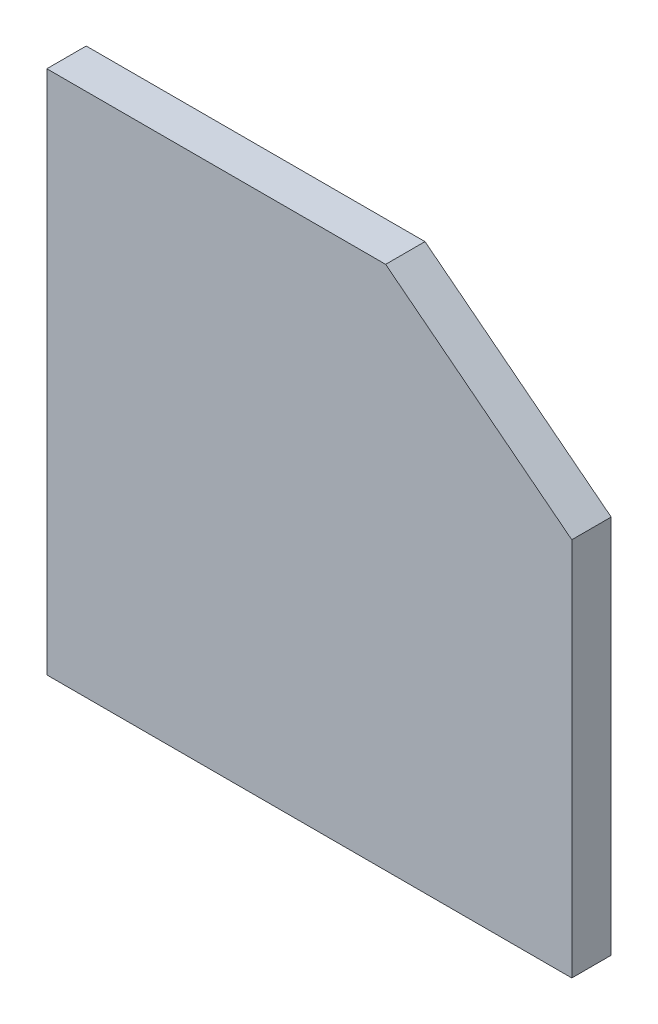
SolidWorks part; units mm, degrees
ref_plane "Front Plane" through (0, 0, 0) normal (0, 0, 1) x (1, 0, 0)
ref_plane "Top Plane" through (0, 0, 0) normal (0, 1, 0) x (1, 0, 0)
ref_plane "Right Plane" through (0, 0, 0) normal (1, 0, 0) x (0, 0, -1)
sketch "Sketch1" plane through (0, 0, 0) normal (0, 0, 1) x (1, 0, 0)
  line L0 (25.8158, 40) -> (40, 28.9181)
  line L1 (0, 0) -> (40, 0)
  line L2 (0, 0) -> (0, 40)
  line L3 (0, 40) -> (40, 40)
  line L4 (40, 0) -> (40, 40)
  dimension "D1" = 40
  dimension "D2" = 40
  dimension "D3" = 38
  dimension "D4" = 18
extrude "Boss-Extrude1" add sketch "Sketch1" along normal blind 3 contours L1 L4 L0 L3 L2 region at (19.2111, 19.1577, 0)
